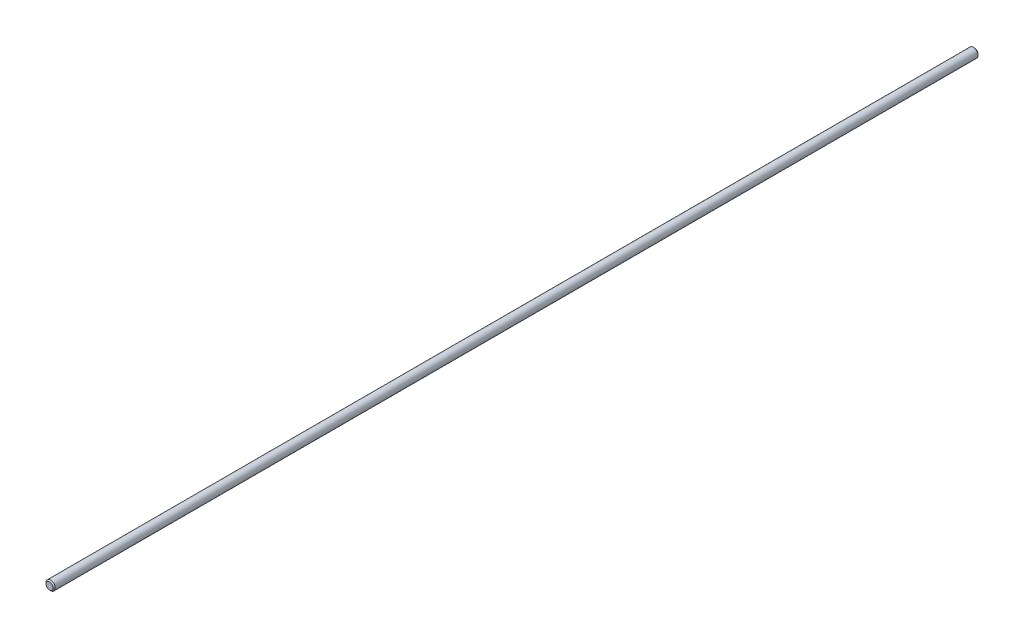
SolidWorks part; units mm, degrees
ref_plane "Front Plane" through (0, 0, 0) normal (0, 0, 1) x (1, 0, 0)
ref_plane "Top Plane" through (0, 0, 0) normal (0, 1, 0) x (1, 0, 0)
ref_plane "Right Plane" through (0, 0, 0) normal (1, 0, 0) x (0, 0, -1)
sketch "Sketch1" plane through (0, 0, 0) normal (1, 0, 0) x (0, 0, -1)
  line L1 (-250, 2.5) -> (250, 2.5)
  line L2 (-250, 2.5) -> (-250, 0)
  line L3 (-250, 0) -> (250, 0) construction
  line L4 (250, 2.5) -> (250, 0)
  point P4 (0, 0)
  point P5 (-249.2, 2.5)
  point P7 (-209.2, 2.5)
  point P8 (248, 2.5)
  point P9 (248, -2.5)
  dimension "Thread Diameter" = 5
  dimension "Length" = 500
  dimension "Thread Pitch" = 0.8
  dimension "Segment Length" = 40.8
  dimension "D1" = 2
sketch "Sketch2" plane through (0, 0, 0) normal (1, 0, 0) x (0, 0, -1)
  line L1 (-250, 0) -> (250, 0)
  line L2 (-250, 0) -> (-250, 2.5)
  line L3 (-250, 2.5) -> (250, 2.5)
  line L4 (250, 0) -> (250, 2.5)
revolve "Revolve1" add sketch "Sketch2" angle 360 about L1
chamfer "Chamfer1" distance 0.6 angle 45 2 edges at (2.5, 0, -250) (2.5, 0, 250)
sketch "Drawing Reference 1" plane through (0, 0, 0) normal (1, 0, 0) x (0, 0, -1)
  line L0 (-250, 2.5) -> (250, 2.5) construction
  line L1 (-250, 2.5) -> (-250, 0) construction
  line L2 (250, 2.5) -> (250, 0) construction
  point P0 (-246.25, 2.5)
  point P1 (246.25, 2.5)
  dimension "D1" = 3.75
  dimension "D2" = 3.75
sketch "Sketch3" [suppressed] plane through (0, 0, -250) normal (0, 0, -1) x (-1, 0, 0)
  circle A0 centre (0, 0) radius 2.5 construction
  circle A1 centre (0, 0) radius 2.5
curve "Helix/Spiral1" [suppressed] pitch 0.8 height 41.6 turns 52
sketch "Sketch4" [suppressed] plane through (0, 0, 0) normal (1, 0, 0) x (0, 0, -1)
  line L0 (249.95, 2.5866) -> (250.35, 1.8938) construction
  line L1 (250.35, 1.8938) -> (250.75, 2.5866) construction
  line L2 (250.75, 2.5866) -> (249.95, 2.5866) construction
  line L3 (249.975, 2.5433) -> (250.725, 2.5433)
  line L4 (250.725, 2.5433) -> (250.4, 1.9804)
  line L5 (250.4, 1.9804) -> (250.3, 1.9804)
  line L6 (250.3, 1.9804) -> (249.975, 2.5433)
  line L7 (250.35, 1.9804) -> (250.35, 1.8938) construction
  line L8 (250, 2.5) -> (250.7, 2.5) construction
  line L9 (250.35, 2.5866) -> (250.35, 2.5) construction
  point P12 (250.35, 2.5433)
  dimension "D1" = 0.8
sweep "Cut-Sweep1" [suppressed] cut profiles "Sketch4" path "Helix/Spiral1"
pattern_linear "LPattern1" [suppressed] of bodies 105
equation "\"D1@Chamfer1\"=0.75*\"Thread Pitch@Sketch1\""
equation "\"Segment Length@Sketch1\"=\"Thread Pitch@Sketch1\"*51"
equation "\"D4@Helix/Spiral1\"=\"Thread Pitch@Sketch1\""
equation "\"D5@Helix/Spiral1\"=(\"Segment Length@Sketch1\"/\"Thread Pitch@Sketch1\")+1"
equation "\"D2@Sketch4\"=\"D1@Sketch4\"/8"
equation "\"D1@Sketch4\"=\"Thread Pitch@Sketch1\""
equation "\"D3@LPattern1\"=\"Segment Length@Sketch1\""
equation "\"D1@Drawing Reference 1\"=\"Thread Diameter@Sketch1\"*0.75"
equation "\"D2@Drawing Reference 1\" = \"D1@Drawing Reference 1\""
equation "\"D1@Sketch1\"=2.5*\"Thread Pitch@Sketch1\""
